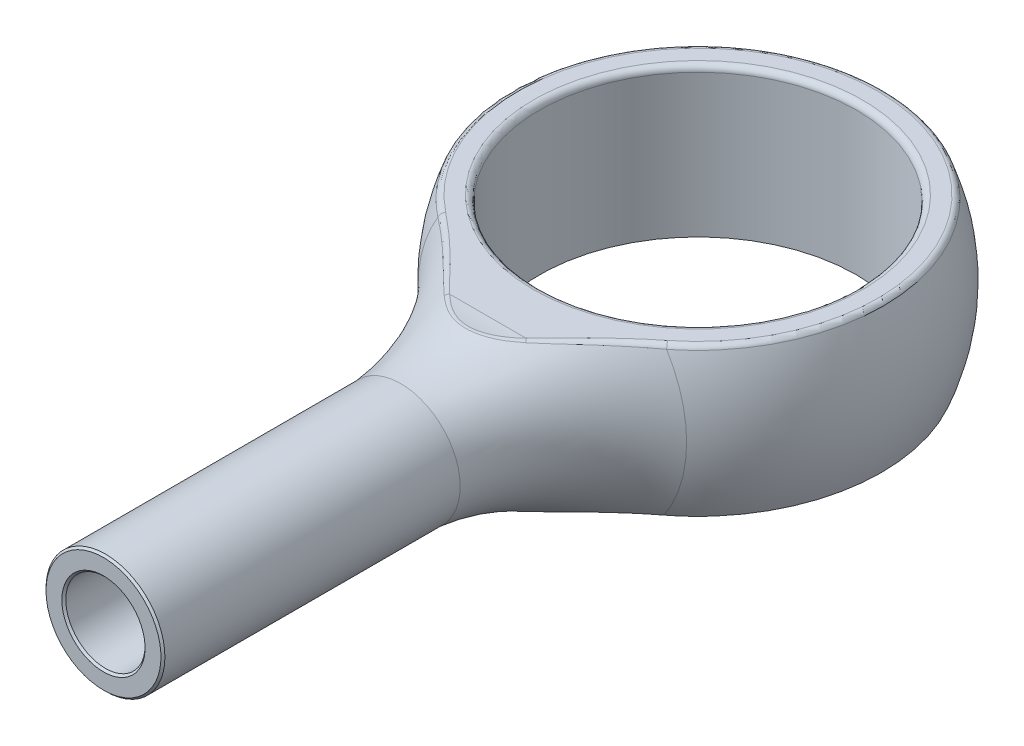
SolidWorks part; units mm, degrees
ref_plane "Front Plane" through (0, 0, 0) normal (0, 0, 1) x (1, 0, 0)
ref_plane "Top Plane" through (0, 0, 0) normal (0, 1, 0) x (1, 0, 0)
ref_plane "Right Plane" through (0, 0, 0) normal (1, 0, 0) x (0, 0, -1)
sketch "Sketch1" plane through (0, 0, 0) normal (0, 1, 0) x (1, 0, 0)
  line L1 (-1.5, -15) -> (-1.5, -7.5)
  line L2 (1.5, -15) -> (1.5, -7.5)
  line L3 (0, -15) -> (0, 5)
  line L5 (-1.5, -15) -> (1.5, -15)
  circle A0 centre (0, 0) radius 2 construction
  arc A2 (3.3896, -3.6757) -> (-3.3896, -3.6757) centre (0, 0) ccw
  arc A3 (-1.5, -7.5) -> (-3.3896, -3.6757) centre (-7.4199, -8.046) ccw
  circle A4 centre (0, 0) radius 4
  arc A5 (1.5, -7.5) -> (3.3896, -3.6757) centre (7.4199, -8.046) cw
  dimension "D1" = 4
  dimension "D2" = 8
  dimension "D3" = 10
sketch "Sketch5" plane through (0, 0, 0) normal (0, 1, 0) x (1, 0, 0)
  line L0 (-1.5, -15) -> (1.5, -15) construction
  line L2 (-1.5, -15) -> (-1.5, -7.5) construction
  line L3 (0, -15) -> (0, 5) construction
  line L4 (-1.5, -15) -> (0, -15)
  line L6 (-1.5, -15) -> (-1.5, -7.5)
  line L7 (0, -15) -> (0, 5)
  arc A1 (-1.5, -7.5) -> (-3.3896, -3.6757) centre (-7.4199, -8.046) ccw construction
  arc A4 (3.3896, -3.6757) -> (-3.3896, -3.6757) centre (0, 0) ccw construction
  arc A6 (-1.5, -7.5) -> (-3.3896, -3.6757) centre (-7.4199, -8.046) ccw
  arc A9 (0, 5) -> (-3.3896, -3.6757) centre (0, 0) ccw
revolve "Revolve2" add sketch "Sketch5" angle 360 about L7
sketch "Sketch6" plane through (0, 0, 0) normal (1, 0, 0) x (0, 0, -1)
  line L0 (0, 0) -> (6.2253, 0) construction
  line L1 (-19.5673, 10.7588) -> (14.9021, 10.7588)
  line L2 (14.9021, 10.7588) -> (14.9021, 1.875)
  line L3 (14.9021, 1.875) -> (-5.3034, 1.875)
  line L4 (-8.1713, 2.7792) -> (-19.5673, 10.7588)
  line L5 (-8.1713, -2.7792) -> (-19.5673, -10.7588)
  line L6 (14.9021, -1.875) -> (-5.3034, -1.875)
  line L7 (14.9021, -10.7588) -> (14.9021, -1.875)
  line L8 (-19.5673, -10.7588) -> (14.9021, -10.7588)
  arc A0 (-5.3034, 1.875) -> (-8.1713, 2.7792) centre (-5.3034, 6.875) cw
  arc A1 (-5.3034, -1.875) -> (-8.1713, -2.7792) centre (-5.3034, -6.875) ccw
  dimension "D1" = 5
  dimension "D2" = 145
  dimension "D3" = 3.75
  dimension "D4" = 1.875
extrude "Cut-Extrude3" cut sketch "Sketch6" against normal blind 10 and the other way blind 10
sketch "Sketch7" plane through (0, 0, 0) normal (0, 1, 0) x (1, 0, 0)
  circle A0 centre (0, 0) radius 4 construction
  circle A1 centre (0, 0) radius 4
extrude "Cut-Extrude4" cut sketch "Sketch7" against normal blind 10 and the other way blind 10
fillet "Fillet1" radius 0.15 5 edges at (0, 1.875, 4) (-0.0966, 1.9024, 5.8262) (0, 1.875, -4.6351)
sketch "Sketch8" plane through (0, 0, 15) normal (0, 0, 1) x (1, 0, 0)
  circle A0 centre (0, 0) radius 1
  dimension "D1" = 2
extrude "Cut-Extrude5" cut sketch "Sketch8" against normal blind 5
chamfer "Chamfer1" distance 0.05 angle 45 2 edges at (1.5, 0, 15) (1, 0, 15)
